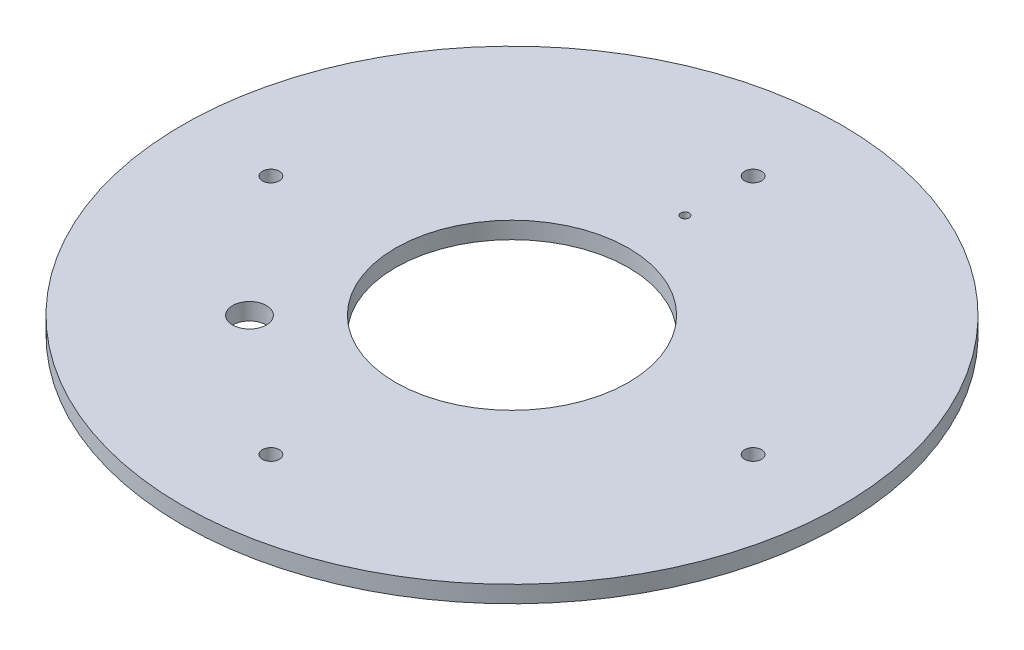
SolidWorks part; units mm, degrees
material "1060 Alloy"
ref_plane "Front Plane" through (0, 0, 0) normal (0, 0, 1) x (1, 0, 0)
ref_plane "Top Plane" through (0, 0, 0) normal (0, 1, 0) x (1, 0, 0)
ref_plane "Right Plane" through (0, 0, 0) normal (1, 0, 0) x (0, 0, -1)
sketch "Sketch1" plane through (0, 0, 0) normal (0, 1, 0) x (1, 0, 0)
  circle A0 centre (0, 0) radius 19.53
  circle A1 centre (0, 0) radius 6.9
  dimension "D1" = 39.06
  dimension "D2" = 13.8
extrude "Boss-Extrude1" add sketch "Sketch1" along normal blind 1
hole_wizard "CSK for M2 Flat Head Machine Screw1" positions "Sketch2" profile "Sketch3" countersink size "M2" standard "ANSI Metric" end condition through all
sketch "Sketch2" plane through (0, 0, 0) normal (0, -1, 0) x (-1, 0, 0)
  point P0 (0, -14.29)
  point P2 (-14.29, 0)
  point P4 (0, 14.29)
  point P28 (14.29, 0)
  dimension "D1" = 14.29
  dimension "D2" = 14.29
  dimension "D3" = 14.29
  dimension "D4" = 14.29
sketch "Sketch3" plane through (0, 0, 14.29) normal (1, 0, 0) x (0, 0, -1)
  line L0 (0, 0) -> (0, 1)
  line L1 (0, 1) -> (0.5, 1)
  line L2 (0.5, 1) -> (0.5, 0.2517)
  line L3 (0.5, 0.2517) -> (0.8, 0)
  line L5 (0.8, 0) -> (0, 0)
  line L6 (-0.5, 0.2517) -> (-0.8, 0) construction
  line L11 (0, -6.35) -> (0, 107.95) construction
  dimension "Thru Hole Dia." = 1
  dimension "Thru Hole Depth" = 1
  dimension "Near C'Sink Dia." = 1.6
  dimension "Near C'Sink Angle" = 100
sketch "Sketch4" plane through (0, 1, 0) normal (0, 1, 0) x (1, 0, 0)
  line L0 (0, 0) -> (-13.4332, -13.4332) construction
  circle A0 centre (0, 10.25) radius 0.25
  circle A1 centre (-7.7782, -7.7782) radius 1
  dimension "D1" = 0.5
  dimension "D2" = 10.25
  dimension "D4" = 2
  dimension "D3" = 11
  dimension "D5" = 0
extrude "Cut-Extrude1" cut sketch "Sketch4" against normal through all both and the other way through all
